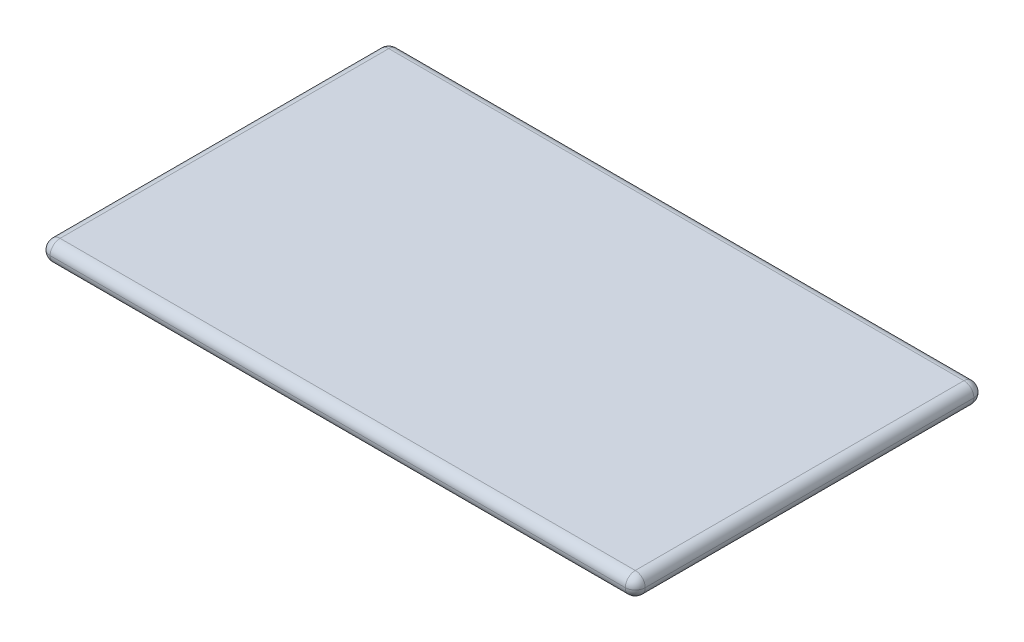
SolidWorks part; units mm, degrees
material "Brass"
ref_plane "Front Plane" through (0, 0, 0) normal (0, 0, 1) x (1, 0, 0)
ref_plane "Top Plane" through (0, 0, 0) normal (0, 1, 0) x (1, 0, 0)
ref_plane "Right Plane" through (0, 0, 0) normal (1, 0, 0) x (0, 0, -1)
sketch "Sketch1" plane through (0, 0, 0) normal (0, 0, 1) x (1, 0, 0)
  line L1 (-6.0706, 0.2032) -> (6.0706, 0.2032)
  line L2 (-6.0706, 0.2032) -> (-6.0706, -0.2032)
  line L3 (-6.0706, -0.2032) -> (6.0706, -0.2032)
  line L4 (6.0706, 0.2032) -> (6.0706, -0.2032)
  line L5 (-6.0706, 0.2032) -> (6.0706, -0.2032) construction
  line L6 (-6.0706, -0.2032) -> (6.0706, 0.2032) construction
  line L9 (-6.4262, -0.2032) -> (-6.0706, -0.2032)
  line L16 (5.6642, -0.2032) -> (6.0706, -0.2032)
  point P0 (0, 0)
  dimension "D1" = 0.4064
  dimension "D2" = 12.1412
extrude "Boss-Extrude1" add sketch "Sketch1" along normal mid plane 7.112 contours L4 L1 L2 L3 | L3 | L3 region at (0, 0, 0)
fillet "Fillet3" radius 0.2032 12 edges at (0, -0.2032, -3.556) (0, 0.2032, -3.556) (0, -0.2032, 3.556) (0, 0.2032, 3.556) (-6.0706, 0, -3.556) (6.0706, 0, -3.556) (-6.0706, 0, 3.556) (6.0706, 0, 3.556) (6.0706, -0.2032, 0) (6.0706, 0.2032, 0) (-6.0706, 0.2032, 0) (-6.0706, -0.2032, 0)
